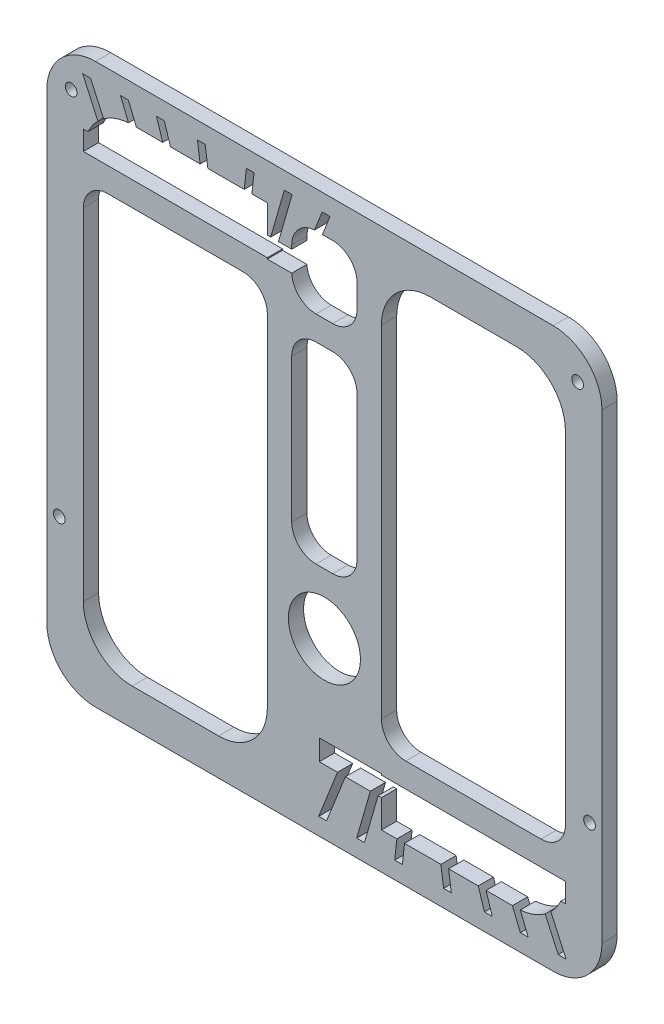
SolidWorks part; units mm, degrees
ref_plane "Front Plane" through (0, 0, 0) normal (0, 0, 1) x (1, 0, 0)
ref_plane "Top Plane" through (0, 0, 0) normal (0, 1, 0) x (1, 0, 0)
ref_plane "Right Plane" through (0, 0, 0) normal (1, 0, 0) x (0, 0, -1)
sketch "Sketch1" plane through (0, 0, 0) normal (0, 0, 1) x (1, 0, 0)
  line L0 (-9.8234, 46.8856) -> (-9.8234, 43.0756) construction
  line L1 (-16.441, -11.4046) -> (41.4264, -11.4046)
  line L2 (-16.441, -11.4046) -> (-16.441, 46.8856)
  line L3 (-16.441, 46.8856) -> (41.4264, 46.8856)
  line L4 (41.4264, -11.4046) -> (41.4264, 46.8856)
  line L6 (-9.8234, 44.9806) -> (-20.2694, 44.9806) construction
  line L7 (-11.9578, 44.9806) -> (-12.504, 44.9806) construction
  line L8 (36.4915, -7.5946) -> (36.4915, -11.4046) construction
  line L10 (-12.631, 43.0756) -> (37.6164, 43.0756)
  line L11 (-12.631, 43.0756) -> (-12.631, -7.5946)
  line L12 (-12.631, -7.5946) -> (37.6164, -7.5946)
  line L13 (37.6164, 43.0756) -> (37.6164, -7.5946)
  line L14 (36.4915, -9.4996) -> (50.994, -9.4996) construction
  line L15 (36.9432, -9.4996) -> (37.4894, -9.4996) construction
  line L16 (37.6164, 41.4945) -> (41.4264, 41.4945) construction
  line L17 (39.5214, 41.4945) -> (39.5214, -21.3698) construction
  line L18 (39.5214, 23.3666) -> (39.5214, 35.6094) construction
  line L19 (-12.631, 40.8837) -> (-16.441, 40.8837) construction
  line L20 (-14.536, 40.8837) -> (-14.536, -26.4843) construction
  line L21 (-14.536, 12.1144) -> (-14.536, -0.1284) construction
  dimension "D1" = 3.81
  dimension "D2" = 3.81
extrude "Boss-Extrude1" add sketch "Sketch1" along normal blind 1.5875
fillet "Fillet3" radius 5.08 4 edges at (37.6164, -7.5946, 0.7937) (-12.631, -7.5946, 0.7937) (37.6164, 43.0756, 0.7937) (-12.631, 43.0756, 0.7937)
sketch "Sketch6" plane through (0, 0, 1.5875) normal (0, 0, 1) x (1, 0, 0)
  line L0 (32.5364, 43.0756) -> (-7.551, 43.0756) construction
  line L1 (-12.631, 37.9956) -> (-12.631, -2.5146) construction
  line L2 (37.6164, -2.5146) -> (37.6164, 37.9956) construction
  line L3 (37.6164, 13.0034) -> (37.6164, 0.405)
  line L4 (18.4394, 43.0756) -> (6.546, 43.0756)
  line L5 (-12.631, 0.405) -> (-12.631, 13.0034)
  line L6 (18.4394, 43.0756) -> (18.4394, -7.5946)
  line L7 (18.4394, -7.5946) -> (6.546, -7.5946)
  line L9 (6.546, 43.0756) -> (6.546, -7.5946)
  line L10 (-7.551, -7.5946) -> (32.5364, -7.5946) construction
  line L11 (8.7335, 6.7042) -> (8.7335, 12.2237) construction
  line L12 (16.2519, 6.7042) -> (16.2519, 13.4807) construction
  line L13 (6.546, 31.0374) -> (6.546, -0.1284) construction
  line L14 (18.4394, 4.4436) -> (18.4394, 35.6094) construction
  circle A0 centre (12.4927, 6.7042) radius 3.7592 construction
  circle A1 centre (12.4927, 6.7042) radius 3.7592
extrude "Boss-Extrude2" add sketch "Sketch6" against normal up to surface (1.5875 mm away) contours L4 L9 L7 L6 A1 up to face at (12.4927, 17.7405, 0)
sketch "Sketch4" plane through (0, 0, 1.5875) normal (0, 0, 1) x (1, 0, 0)
  line L0 (-12.631, 40.1546) -> (-12.631, 37.9956)
  line L1 (-12.631, 37.9956) -> (13.023, 37.9956)
  line L2 (13.023, 37.9956) -> (13.023, 40.1546)
  line L3 (13.023, 40.1546) -> (11.127, 40.1546)
  line L4 (11.127, 40.1546) -> (13.0827, 45.1076)
  line L5 (13.0827, 45.1076) -> (12.2634, 45.1076)
  line L6 (18.4394, 35.6094) -> (18.4394, 4.4436) construction
  line L7 (18.4394, 4.4436) -> (37.4894, 4.4436) construction
  line L8 (37.4894, 4.4436) -> (37.4894, 35.6094) construction
  line L9 (-12.504, 40.0276) -> (-12.504, 38.1226) construction
  line L10 (-12.504, 38.1226) -> (12.896, 38.1226) construction
  line L11 (12.896, 38.1226) -> (12.896, 40.0276) construction
  line L12 (12.896, 40.0276) -> (10.9403, 40.0276) construction
  line L13 (10.9403, 40.0276) -> (12.896, 44.9806) construction
  line L14 (12.896, 44.9806) -> (12.3498, 44.9806) construction
  line L15 (12.3498, 44.9806) -> (10.3941, 40.0276) construction
  line L16 (10.3941, 40.0276) -> (7.5365, 40.0276) construction
  line L17 (7.5365, 40.0276) -> (8.959, 44.9806) construction
  line L18 (8.959, 44.9806) -> (8.4128, 44.9806) construction
  line L19 (8.4128, 44.9806) -> (6.9904, 40.0276) construction
  line L20 (6.9904, 40.0276) -> (4.4758, 40.0276) construction
  line L21 (4.4758, 40.0276) -> (5.022, 44.9806) construction
  line L22 (5.022, 44.9806) -> (4.4758, 44.9806) construction
  line L23 (4.4758, 44.9806) -> (3.9297, 40.0276) construction
  line L24 (3.9297, 40.0276) -> (0.6404, 40.0276) construction
  line L25 (0.6404, 40.0276) -> (-0.0452, 44.9806) construction
  line L26 (-0.0452, 44.9806) -> (-0.5914, 44.9806) construction
  line L27 (-0.5914, 44.9806) -> (0.0943, 40.0276) construction
  line L28 (0.0943, 40.0276) -> (-2.7124, 40.0276) construction
  line L29 (-2.7124, 40.0276) -> (-4.287, 44.9806) construction
  line L30 (-4.287, 44.9806) -> (-4.8332, 44.9806) construction
  line L31 (-4.8332, 44.9806) -> (-3.2585, 40.0276) construction
  line L32 (-3.2585, 40.0276) -> (-6.0144, 40.0276) construction
  line L33 (-6.0144, 40.0276) -> (-8.0208, 44.9806) construction
  line L34 (-8.0208, 44.9806) -> (-8.567, 44.9806) construction
  line L35 (-8.567, 44.9806) -> (-6.5605, 40.0276) construction
  line L36 (-6.5605, 40.0276) -> (-9.71, 40.0276) construction
  line L37 (-9.71, 40.0276) -> (-11.9578, 44.9806) construction
  line L38 (-11.9578, 44.9806) -> (-12.504, 44.9806) construction
  line L39 (-12.504, 44.9806) -> (-10.2562, 40.0276) construction
  line L40 (-10.2562, 40.0276) -> (-12.504, 40.0276) construction
  line L41 (12.2634, 45.1076) -> (10.3077, 40.1546)
  line L42 (10.3077, 40.1546) -> (7.7051, 40.1546)
  line L43 (7.7051, 40.1546) -> (9.1276, 45.1076)
  line L44 (9.1276, 45.1076) -> (8.3172, 45.1076)
  line L45 (8.3172, 45.1076) -> (6.8947, 40.1546)
  line L46 (6.8947, 40.1546) -> (4.6176, 40.1546)
  line L47 (18.4394, 35.6094) -> (18.4394, 4.4436)
  line L48 (18.4394, 4.4436) -> (37.4894, 4.4436)
  line L49 (37.4894, 4.4436) -> (37.4894, 35.6094)
  line L50 (-12.504, 40.0276) -> (-12.504, 38.1226) construction
  line L51 (-12.504, 38.1226) -> (12.896, 38.1226) construction
  line L52 (12.896, 38.1226) -> (12.896, 40.0276) construction
  line L53 (12.896, 40.0276) -> (10.9403, 40.0276) construction
  line L54 (10.9403, 40.0276) -> (12.896, 44.9806) construction
  line L55 (12.896, 44.9806) -> (12.3498, 44.9806) construction
  line L56 (12.3498, 44.9806) -> (10.3941, 40.0276) construction
  line L57 (10.3941, 40.0276) -> (7.5365, 40.0276) construction
  line L58 (7.5365, 40.0276) -> (8.959, 44.9806) construction
  line L59 (8.959, 44.9806) -> (8.4128, 44.9806) construction
  line L60 (8.4128, 44.9806) -> (6.9904, 40.0276) construction
  line L61 (6.9904, 40.0276) -> (4.4758, 40.0276) construction
  line L62 (4.4758, 40.0276) -> (5.022, 44.9806) construction
  line L63 (5.022, 44.9806) -> (4.4758, 44.9806) construction
  line L64 (4.4758, 44.9806) -> (3.9297, 40.0276) construction
  line L65 (3.9297, 40.0276) -> (0.6404, 40.0276) construction
  line L66 (0.6404, 40.0276) -> (-0.0452, 44.9806) construction
  line L67 (-0.0452, 44.9806) -> (-0.5914, 44.9806) construction
  line L68 (-0.5914, 44.9806) -> (0.0943, 40.0276) construction
  line L69 (0.0943, 40.0276) -> (-2.7124, 40.0276) construction
  line L70 (-2.7124, 40.0276) -> (-4.287, 44.9806) construction
  line L71 (-4.287, 44.9806) -> (-4.8332, 44.9806) construction
  line L72 (-4.8332, 44.9806) -> (-3.2585, 40.0276) construction
  line L73 (-3.2585, 40.0276) -> (-6.0144, 40.0276) construction
  line L74 (-6.0144, 40.0276) -> (-8.0208, 44.9806) construction
  line L75 (-8.0208, 44.9806) -> (-8.567, 44.9806) construction
  line L76 (-8.567, 44.9806) -> (-6.5605, 40.0276) construction
  line L77 (-6.5605, 40.0276) -> (-9.71, 40.0276) construction
  line L78 (-9.71, 40.0276) -> (-11.9578, 44.9806) construction
  line L79 (-11.9578, 44.9806) -> (-12.504, 44.9806) construction
  line L80 (-12.504, 44.9806) -> (-10.2562, 40.0276) construction
  line L81 (-10.2562, 40.0276) -> (-12.504, 40.0276) construction
  line L82 (4.6176, 40.1546) -> (5.1638, 45.1076)
  line L83 (5.1638, 45.1076) -> (4.3621, 45.1076)
  line L84 (4.3621, 45.1076) -> (3.8159, 40.1546)
  line L85 (3.8159, 40.1546) -> (0.7511, 40.1546)
  line L86 (0.7511, 40.1546) -> (0.0654, 45.1076)
  line L87 (0.0654, 45.1076) -> (-0.7372, 45.1076)
  line L88 (-14.5106, -1.1684) -> (37.4894, -1.1684)
  line L89 (37.4894, -1.1684) -> (37.4894, -0.1284)
  line L90 (37.4894, -0.1284) -> (6.546, -0.1284)
  line L91 (6.546, -0.1284) -> (-12.504, -0.1284)
  line L92 (-12.504, -0.1284) -> (-14.5106, -0.1284)
  line L93 (-14.5106, -0.1284) -> (-14.5106, -1.1684)
  line L94 (-0.7372, 45.1076) -> (-0.0515, 40.1546)
  line L95 (37.4894, -1.1684) -> (37.4894, -0.1284)
  line L96 (-0.0515, 40.1546) -> (-2.6195, 40.1546)
  line L97 (-2.6195, 40.1546) -> (-4.1941, 45.1076)
  line L98 (-4.1941, 45.1076) -> (-5.0068, 45.1076)
  line L99 (-5.0068, 45.1076) -> (-3.4322, 40.1546)
  line L100 (-3.4322, 40.1546) -> (-5.9288, 40.1546)
  line L101 (-5.9288, 40.1546) -> (-7.9353, 45.1076)
  line L102 (-7.9353, 45.1076) -> (-8.7555, 45.1076)
  line L103 (-8.7555, 45.1076) -> (-6.749, 40.1546)
  line L104 (-6.749, 40.1546) -> (-9.6282, 40.1546)
  line L105 (-9.6282, 40.1546) -> (-11.876, 45.1076)
  line L106 (-11.876, 45.1076) -> (-12.7011, 45.1076)
  line L107 (-12.7011, 45.1076) -> (-10.4533, 40.1546)
  line L108 (-10.4533, 40.1546) -> (-12.631, 40.1546)
  line L114 (37.4894, -4.5466) -> (37.4894, -2.6416)
  line L115 (37.4894, -2.6416) -> (12.0894, -2.6416)
  line L116 (12.0894, -2.6416) -> (12.0894, -4.5466)
  line L117 (12.0894, -4.5466) -> (14.0451, -4.5466)
  line L118 (14.0451, -4.5466) -> (12.0894, -9.4996)
  line L119 (12.0894, -9.4996) -> (12.6356, -9.4996)
  line L120 (12.6356, -9.4996) -> (14.5913, -4.5466)
  line L121 (14.5913, -4.5466) -> (17.4489, -4.5466)
  line L122 (17.4489, -4.5466) -> (16.0264, -9.4996)
  line L123 (16.0264, -9.4996) -> (16.5726, -9.4996)
  line L124 (16.5726, -9.4996) -> (17.995, -4.5466)
  line L125 (17.995, -4.5466) -> (20.5096, -4.5466)
  line L126 (20.5096, -4.5466) -> (19.9634, -9.4996)
  line L127 (19.9634, -9.4996) -> (20.5096, -9.4996)
  line L128 (20.5096, -9.4996) -> (21.0557, -4.5466)
  line L129 (21.0557, -4.5466) -> (24.345, -4.5466)
  line L130 (24.345, -4.5466) -> (25.0306, -9.4996)
  line L131 (25.0306, -9.4996) -> (25.5768, -9.4996)
  line L132 (25.5768, -9.4996) -> (24.8911, -4.5466)
  line L133 (24.8911, -4.5466) -> (27.6978, -4.5466)
  line L134 (27.6978, -4.5466) -> (29.2724, -9.4996)
  line L135 (29.2724, -9.4996) -> (29.8186, -9.4996)
  line L136 (29.8186, -9.4996) -> (28.2439, -4.5466)
  line L137 (28.2439, -4.5466) -> (30.9998, -4.5466)
  line L138 (30.9998, -4.5466) -> (33.0062, -9.4996)
  line L139 (33.0062, -9.4996) -> (33.5524, -9.4996)
  line L140 (33.5524, -9.4996) -> (31.5459, -4.5466)
  line L141 (31.5459, -4.5466) -> (34.6954, -4.5466)
  line L142 (34.6954, -4.5466) -> (36.9432, -9.4996)
  line L143 (36.9432, -9.4996) -> (37.4894, -9.4996)
  line L144 (37.4894, -9.4996) -> (35.2416, -4.5466)
  line L145 (35.2416, -4.5466) -> (37.4894, -4.5466)
  line L146 (37.4894, -4.5466) -> (37.4894, -2.6416) construction
  line L147 (37.4894, -2.6416) -> (12.0894, -2.6416) construction
  line L148 (12.0894, -2.6416) -> (12.0894, -4.5466) construction
  line L149 (12.0894, -4.5466) -> (14.0451, -4.5466) construction
  line L150 (14.0451, -4.5466) -> (12.0894, -9.4996) construction
  line L151 (12.0894, -9.4996) -> (12.6356, -9.4996) construction
  line L152 (12.6356, -9.4996) -> (14.5913, -4.5466) construction
  line L153 (14.5913, -4.5466) -> (17.4489, -4.5466) construction
  line L154 (17.4489, -4.5466) -> (16.0264, -9.4996) construction
  line L155 (16.0264, -9.4996) -> (16.5726, -9.4996) construction
  line L156 (16.5726, -9.4996) -> (17.995, -4.5466) construction
  line L157 (17.995, -4.5466) -> (20.5096, -4.5466) construction
  line L158 (20.5096, -4.5466) -> (19.9634, -9.4996) construction
  line L159 (19.9634, -9.4996) -> (20.5096, -9.4996) construction
  line L160 (20.5096, -9.4996) -> (21.0557, -4.5466) construction
  line L161 (21.0557, -4.5466) -> (24.345, -4.5466) construction
  line L162 (24.345, -4.5466) -> (25.0306, -9.4996) construction
  line L163 (25.0306, -9.4996) -> (25.5768, -9.4996) construction
  line L164 (25.5768, -9.4996) -> (24.8911, -4.5466) construction
  line L165 (24.8911, -4.5466) -> (27.6978, -4.5466) construction
  line L166 (27.6978, -4.5466) -> (29.2724, -9.4996) construction
  line L167 (29.2724, -9.4996) -> (29.8186, -9.4996) construction
  line L168 (29.8186, -9.4996) -> (28.2439, -4.5466) construction
  line L169 (28.2439, -4.5466) -> (30.9998, -4.5466) construction
  line L170 (30.9998, -4.5466) -> (33.0062, -9.4996) construction
  line L171 (33.0062, -9.4996) -> (33.5524, -9.4996) construction
  line L172 (33.5524, -9.4996) -> (31.5459, -4.5466) construction
  line L173 (31.5459, -4.5466) -> (34.6954, -4.5466) construction
  line L174 (34.6954, -4.5466) -> (36.9432, -9.4996) construction
  line L175 (36.9432, -9.4996) -> (37.4894, -9.4996) construction
  line L176 (37.4894, -9.4996) -> (35.2416, -4.5466) construction
  line L177 (35.2416, -4.5466) -> (37.4894, -4.5466) construction
  line L211 (37.6164, -4.6736) -> (37.6164, -2.5146)
  line L212 (37.6164, -2.5146) -> (11.9624, -2.5146)
  line L213 (11.9624, -2.5146) -> (11.9624, -4.6736)
  line L214 (11.9624, -4.6736) -> (13.8584, -4.6736)
  line L215 (13.8584, -4.6736) -> (11.9027, -9.6266)
  line L216 (11.9027, -9.6266) -> (12.722, -9.6266)
  line L217 (12.722, -9.6266) -> (14.6777, -4.6736)
  line L218 (14.6777, -4.6736) -> (17.2803, -4.6736)
  line L219 (17.2803, -4.6736) -> (15.8578, -9.6266)
  line L220 (15.8578, -9.6266) -> (16.6682, -9.6266)
  line L221 (16.6682, -9.6266) -> (18.0907, -4.6736)
  line L222 (18.0907, -4.6736) -> (20.3678, -4.6736)
  line L223 (20.3678, -4.6736) -> (19.8216, -9.6266)
  line L224 (19.8216, -9.6266) -> (20.6233, -9.6266)
  line L225 (20.6233, -9.6266) -> (21.1695, -4.6736)
  line L226 (21.1695, -4.6736) -> (24.2343, -4.6736)
  line L227 (24.2343, -4.6736) -> (24.92, -9.6266)
  line L228 (24.92, -9.6266) -> (25.7226, -9.6266)
  line L229 (25.7226, -9.6266) -> (25.0369, -4.6736)
  line L230 (25.0369, -4.6736) -> (27.6049, -4.6736)
  line L231 (27.6049, -4.6736) -> (29.1795, -9.6266)
  line L232 (29.1795, -9.6266) -> (29.9922, -9.6266)
  line L233 (29.9922, -9.6266) -> (28.4176, -4.6736)
  line L234 (28.4176, -4.6736) -> (30.9142, -4.6736)
  line L235 (30.9142, -4.6736) -> (32.9207, -9.6266)
  line L236 (32.9207, -9.6266) -> (33.7409, -9.6266)
  line L237 (33.7409, -9.6266) -> (31.7344, -4.6736)
  line L238 (31.7344, -4.6736) -> (34.6136, -4.6736)
  line L239 (34.6136, -4.6736) -> (36.8614, -9.6266)
  line L240 (36.8614, -9.6266) -> (37.6865, -9.6266)
  line L241 (37.6865, -9.6266) -> (35.4387, -4.6736)
  line L242 (35.4387, -4.6736) -> (37.6164, -4.6736)
  dimension "D1" = 0
  dimension "D2" = 0
  dimension "D3" = 0.127
  dimension "D4" = 0.127
extrude "Fins cut" cut sketch "Sketch4" against normal blind 2.54
sketch "Sketch7" plane through (0, 0, 1.5875) normal (0, 0, 1) x (1, 0, 0)
  line L0 (-12.631, 40.1546) -> (-12.631, -2.5146) construction
  line L1 (-12.631, 38.1226) -> (6.546, 38.1226)
  line L2 (-12.631, 38.1226) -> (-12.631, 35.5826)
  line L3 (-12.631, 35.5826) -> (6.546, 35.5826)
  line L4 (6.546, 38.1226) -> (6.546, 35.5826)
  line L5 (6.546, 37.9956) -> (6.546, -7.5946) construction
  line L9 (37.6164, -4.6736) -> (37.6164, 37.9956) construction
  line L10 (37.6164, -2.6416) -> (18.4394, -2.6416)
  line L11 (37.6164, -2.6416) -> (37.6164, -0.1016)
  line L12 (37.6164, -0.1016) -> (18.4394, -0.1016)
  line L13 (18.4394, -2.6416) -> (18.4394, -0.1016)
  line L14 (18.4394, 43.0756) -> (18.4394, -2.5146) construction
  line L16 (37.4894, -2.6416) -> (12.0894, -2.6416) construction
  line L19 (-12.504, 38.1226) -> (12.896, 38.1226) construction
  dimension "D1" = 2.54
  dimension "D2" = 2.54
extrude "Boss-Extrude3" add sketch "Sketch7" against normal up to surface (1.5875 mm away) up to face at (24.7833, -3.5085, 0)
fillet "Fillet1" radius 5.08 4 edges at (-16.441, -11.4046, 0.7937) (41.4264, -11.4046, 0.7937) (41.4264, 46.8856, 0.7937) (-16.441, 46.8856, 0.7937)
fillet "Fillet4" radius 5.08 2 edges at (6.546, -7.5946, 0.7937) (18.4394, 43.0756, 0.7937)
sketch "Sketch8" plane through (0, 0, 1.5875) normal (0, 0, 1) x (1, 0, 0)
  line L0 (6.546, 35.5826) -> (6.546, -2.5146) construction
  line L1 (9.086, 43.0756) -> (15.8994, 43.0756)
  line L2 (9.086, 43.0756) -> (9.086, 13.0034)
  line L3 (9.086, 13.0034) -> (15.8994, 13.0034)
  line L4 (15.8994, 43.0756) -> (15.8994, 13.0034)
  line L5 (18.4394, 37.9956) -> (18.4394, -0.1016) construction
  line L7 (12.4927, 10.4634) -> (-0.3555, 10.4634) construction
  line L8 (12.4927, 6.7042) -> (12.4927, 10.4634) construction
  line L9 (6.546, 43.0756) -> (4.9397, 43.0756) construction
  line L10 (9.086, 35.5826) -> (15.8994, 35.5826)
  line L11 (-12.631, 35.5826) -> (6.546, 35.5826) construction
  line L12 (9.086, 33.0426) -> (15.8994, 33.0426)
  circle A1 centre (12.4927, 6.7042) radius 3.7592 construction
  dimension "D1" = 2.54
  dimension "D2" = 2.54
  dimension "D3" = 2.54
  dimension "D4" = 2.54
extrude "Cut-Extrude5" cut sketch "Sketch8" against normal up to surface (1.5875 mm away) contours L2 L10 L4 L1 | L12 L2 L3 L4 up to face at (24.5453, -7.1299, 0)
fillet "Fillet5" radius 2.54 4 edges at (15.8994, 13.0034, 0.7937) (9.086, 13.0034, 0.7937) (15.8994, 43.0756, 0.7937) (9.086, 43.0756, 0.7937)
fillet "Fillet6" radius 2.54 4 edges at (6.546, 35.5826, 0.7937) (18.4394, -0.1016, 0.7937) (37.6164, -0.1016, 0.7937) (-12.631, 35.5826, 0.7937)
fillet "Fillet7" radius 2.54 4 edges at (15.8994, 35.5826, 0.7937) (15.8994, 33.0426, 0.7937) (9.086, 33.0426, 0.7937) (9.086, 35.5826, 0.7937)
sketch "Sketch9" plane through (0, 0, 1.5875) normal (0, 0, 1) x (1, 0, 0)
  line L0 (-14.536, 12.1144) -> (-14.536, -0.1284) construction
  line L1 (-16.441, 41.8056) -> (-16.441, -6.3246) construction
  line L3 (-14.536, 12.1144) -> (-14.536, -0.1284) construction
  line L4 (-15.7552, 3.9102) -> (-16.441, 3.9102) construction
  line L5 (40.7406, 3.9102) -> (41.4264, 3.9102) construction
  line L6 (36.3464, 46.8856) -> (-11.361, 46.8856) construction
  line L7 (41.4264, -6.3246) -> (41.4264, 41.8056) construction
  circle A0 centre (-13.901, 43.0756) radius 0.6096
  circle A1 centre (38.8864, 43.0756) radius 0.6096
  circle A2 centre (40.131, 3.9102) radius 0.6096
  circle A3 centre (-15.1456, 3.9102) radius 0.6096
  circle A4 centre (-11.1293, 4.4182) radius 0.6096 construction
  circle A5 centre (-11.1293, 4.4182) radius 0.6096 construction
  dimension "D1" = 1.2192
  dimension "D2" = 3.81
  dimension "D3" = 2.54
  dimension "D4" = 2.54
  dimension "D5" = 0.508
extrude "Cut-Extrude6" cut sketch "Sketch9" against normal up to surface (1.5875 mm away) up to face at (12.4927, 23.023, 0)
